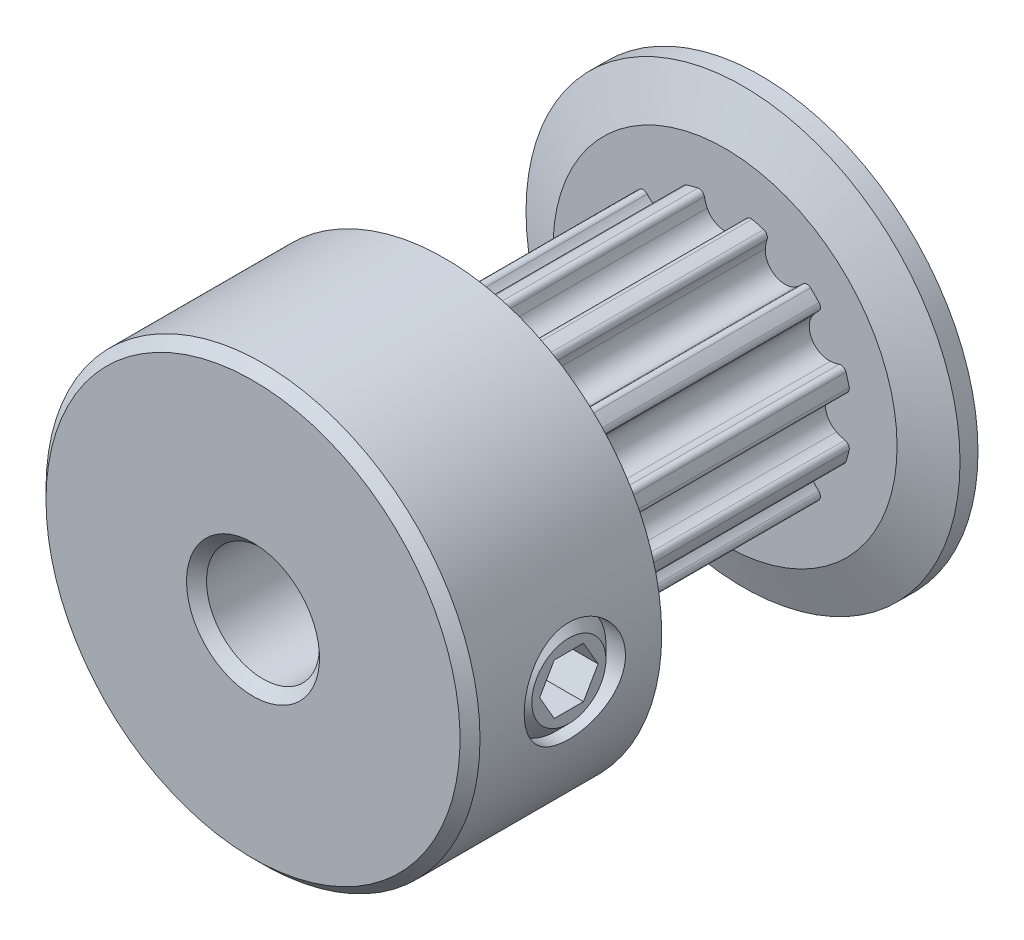
SolidWorks part; units mm, degrees
ref_plane "Front Plane" through (0, 0, 0) normal (0, 0, 1) x (1, 0, 0)
ref_plane "Top Plane" through (0, 0, 0) normal (0, 1, 0) x (1, 0, 0)
ref_plane "Right Plane" through (0, 0, 0) normal (1, 0, 0) x (0, 0, -1)
sketch "Sketch1" plane through (0, 0, 0) normal (0, 0, 1) x (1, 0, 0)
  line L1 (-1.6491, 2.8185) -> (1.6491, 2.8185) construction
  line L4 (0, 0) -> (0, 2.8185) construction
  line L5 (0, 2.8185) -> (0, 9.5178) construction
  line L6 (0, 3.8225) -> (1.9303, 3.2993) construction
  line L7 (1.9303, 3.2993) -> (2.4111, 3.018) construction
  line L8 (1.9303, 3.2993) -> (1.6491, 2.8185) construction
  line L9 (-1.9303, 3.2993) -> (-1.6491, 2.8185) construction
  line L10 (-1.8021, 3.08) -> (-3.5667, 6.096)
  line L11 (-3.5667, 6.096) -> (3.5667, 6.096)
  line L12 (3.5667, 6.096) -> (1.8021, 3.08)
  circle A0 centre (0, 0) radius 3.8225 construction
  circle A1 centre (0, 0) radius 6.096 construction
  circle A2 centre (0, 0) radius 3.5685 construction
  arc A3 (-0.4989, 3.1303) -> (0.4989, 3.1303) centre (0, 3.3735) ccw
  arc A4 (-0.4989, 3.1303) -> (-0.5801, 3.37) centre (0.4, 3.5685) cw
  arc A5 (-1.8021, 3.08) -> (-0.759, 3.4868) centre (0, 0) cw
  arc A6 (-0.5801, 3.37) -> (-0.759, 3.4868) centre (-0.7271, 3.3403) ccw
  arc A7 (1.8021, 3.08) -> (0.759, 3.4868) centre (0, 0) ccw
  arc A8 (0.5801, 3.37) -> (0.759, 3.4868) centre (0.7271, 3.3403) cw
  arc A9 (0.4989, 3.1303) -> (0.5801, 3.37) centre (-0.4, 3.5685) ccw
  point P6 (0, 20.9083)
  point P11 (0, 3.8225)
  point P13 (0, 6.096)
  point P14 (0, 3.5685)
  dimension "D1" = 11.3906
  dimension "D2" = 5.6953
sketch "Sketch2" plane through (0, 0, 0) normal (1, 0, 0) x (0, 0, -1)
  line L0 (-7.135, 1.5875) -> (7.135, 1.5875)
  line L1 (-7.135, 1.5875) -> (-7.135, 6.096)
  line L2 (-1.75, 6.096) -> (-7.135, 6.096)
  line L3 (-2.255, 1.5875) -> (-2.255, 6.096) construction
  line L4 (-2.255, 6.096) -> (-1.245, 6.096) construction
  line L5 (-1.245, 6.096) -> (-1.245, 3.5685) construction
  line L6 (-1.245, 3.5685) -> (6.125, 3.5685)
  line L7 (6.125, 3.5685) -> (6.125, 6.096) construction
  line L8 (6.125, 6.096) -> (7.135, 6.096) construction
  line L9 (7.135, 6.096) -> (7.135, 1.5875)
  line L10 (-7.135, 0) -> (7.135, 0) construction
  line L11 (6.63, 6.096) -> (6.125, 4.8323)
  line L12 (-1.245, 4.8323) -> (-1.75, 6.096)
  line L14 (-1.245, 4.8323) -> (-1.245, 3.5685)
  line L15 (6.125, 3.5685) -> (6.125, 4.8323)
  line L16 (6.63, 6.096) -> (7.135, 6.096)
  arc A0 (-1.245, 4.8323) -> (-1.75, 6.096) centre (-3.0788, 4.8323) ccw construction
  arc A1 (6.125, 4.8323) -> (6.63, 6.096) centre (7.9588, 4.8323) cw construction
  point P12 (-1.245, 4.8323)
  point P14 (-1.75, 6.096)
  point P20 (6.125, 4.8323)
  point P21 (6.63, 6.096)
  point P25 (6.125, 0)
  point P26 (-1.245, 0)
  dimension "OA" = 14.27
  dimension "Bore" = 3.175
  dimension "Outside Width" = 8.38
  dimension "Inside Width" = 7.37
revolve "Revolve1" add sketch "Sketch2" angle 360 mid plane about L10
sketch "Sketch3" plane through (0, 0, 0) normal (0, 0, 1) x (1, 0, 0)
  line L6 (3.5667, 6.096) -> (-3.5667, 6.096)
  line L7 (1.8021, 3.08) -> (3.5667, 6.096)
  line L8 (-3.5667, 6.096) -> (-1.8021, 3.08)
  line L9 (3.5667, 6.096) -> (-3.5667, 6.096)
  line L10 (1.8021, 3.08) -> (3.5667, 6.096)
  line L11 (-3.5667, 6.096) -> (-1.8021, 3.08)
  arc A8 (1.8021, 3.08) -> (0.759, 3.4868) centre (0, 0) ccw
  arc A9 (0.759, 3.4868) -> (0.5801, 3.37) centre (0.7271, 3.3403) ccw
  arc A10 (0.4989, 3.1303) -> (0.5801, 3.37) centre (-0.4, 3.5685) ccw
  arc A11 (-0.4989, 3.1303) -> (0.4989, 3.1303) centre (0, 3.3735) ccw
  arc A12 (-0.5801, 3.37) -> (-0.4989, 3.1303) centre (0.4, 3.5685) ccw
  arc A13 (-0.5801, 3.37) -> (-0.759, 3.4868) centre (-0.7271, 3.3403) ccw
  arc A14 (-0.759, 3.4868) -> (-1.8021, 3.08) centre (0, 0) ccw
  arc A15 (1.8021, 3.08) -> (0.759, 3.4868) centre (0, 0) ccw
  arc A16 (0.759, 3.4868) -> (0.5801, 3.37) centre (0.7271, 3.3403) ccw
  arc A17 (0.4989, 3.1303) -> (0.5801, 3.37) centre (-0.4, 3.5685) ccw
  arc A18 (-0.4989, 3.1303) -> (0.4989, 3.1303) centre (0, 3.3735) ccw
  arc A19 (-0.5801, 3.37) -> (-0.4989, 3.1303) centre (0.4, 3.5685) ccw
  arc A20 (-0.5801, 3.37) -> (-0.759, 3.4868) centre (-0.7271, 3.3403) ccw
  arc A21 (-0.759, 3.4868) -> (-1.8021, 3.08) centre (0, 0) ccw
  dimension "D1" = 0
extrude "Cut-Extrude1" cut sketch "Sketch3" against normal up to vertex (6.125 mm away) from vertex up to point (0, 3.5685, -6.125) starting at point (0, 3.5685, 1.245)
pattern_circular "CirPattern1" count 12 over 360 about axis through (0, 0, 7.135) along (0, 0, 1) of "Cut-Extrude1"
sketch "Sketch4" plane through (0, 0, 0) normal (1, 0, 0) x (0, -1, 0)
  line L0 (0, -1.245) -> (0, -7.135) construction
  line L1 (-1.5875, -7.135) -> (1.5875, -7.135) construction
  line L2 (4.8323, -1.245) -> (-4.8323, -1.245) construction
  circle A0 centre (0, -4.19) radius 1.4224
extrude "Cut-Extrude2" cut sketch "Sketch4" along normal through all
ref_plane "Plane1" through (0, 0, 4.19) normal (0, 0, 1) x (1, 0, 0)
sketch "Sketch5" plane through (0, 0, 4.19) normal (0, 0, 1) x (1, 0, 0)
  line L0 (0, 0) -> (0, 6.096) construction
  line L1 (1.5875, -1.0414) -> (1.5875, 0)
  line L2 (1.9685, -1.4224) -> (5.5467, -1.4224)
  line L3 (1.5875, 0) -> (6.096, 0) construction
  line L4 (1.5875, 0) -> (5.9277, 0)
  line L5 (5.9277, 0) -> (5.9277, -1.0414)
  line L6 (1.9685, -1.4224) -> (1.5875, -1.0414)
  line L7 (5.9277, -1.0414) -> (5.5467, -1.4224)
  circle A0 centre (0, 0) radius 6.096 construction
  circle A1 centre (0, 0) radius 1.5875 construction
  point P2 (1.5875, -1.4224)
  point P11 (5.9277, -1.4224)
revolve "Revolve2" add sketch "Sketch5" angle 360 mid plane about L4
sketch "Sketch6" plane through (5.9277, 5.3841, 0) normal (-1, 0, 0) x (0, -1, 0)
  line L1 (5.3841, 5.0112) -> (4.6729, 4.6006)
  line L2 (4.6729, 4.6006) -> (4.6729, 3.7794)
  line L3 (4.6729, 3.7794) -> (5.3841, 3.3688)
  line L4 (5.3841, 3.3688) -> (6.0953, 3.7794)
  line L5 (6.0953, 3.7794) -> (6.0953, 4.6006)
  line L6 (6.0953, 4.6006) -> (5.3841, 5.0112)
  circle A0 centre (5.3841, 4.19) radius 0.7112 construction
  dimension "D1" = 1.4224
extrude "Cut-Extrude3" cut sketch "Sketch6" along normal blind 1.0668
chamfer "Chamfer1" distance 0.2807 angle 45 2 edges at (1.5875, 0, 7.135) (6.096, 0, 7.135)
ref_axis "Center Axis 1" through (0, 0, -7.135) along (0, 0, 1)
ref_plane "Contact Plane 1" through (0, 0, 7.135) normal (0, 0, 1) x (1, 0, 0)
ref_plane "Contact Plane 2" through (0, 0, -7.135) normal (0, 0, -1) x (-1, 0, 0)
equation "\"D2@Sketch1\"= \"D1@Sketch1\" / 2"
equation "\"D1@Sketch6\" = \"Set Screw@Sketch4\" / 2"
equation "\"D1@Cut-Extrude3\" = \"D1@Sketch6\"*.75"
